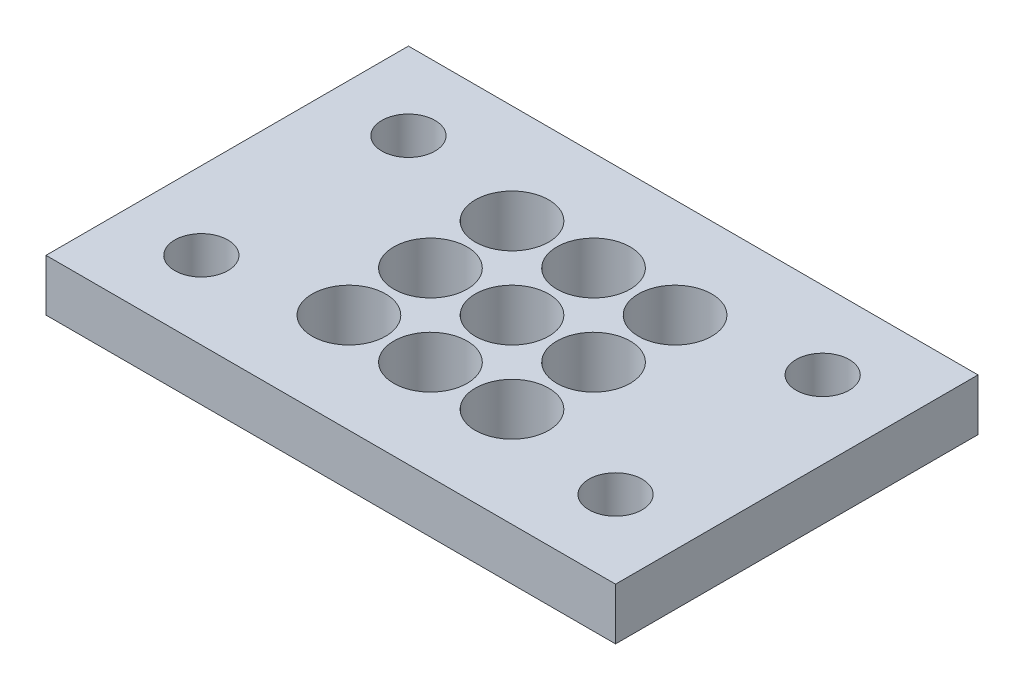
SolidWorks part; units mm, degrees
ref_plane "Front Plane" through (0, 0, 0) normal (0, 0, 1) x (1, 0, 0)
ref_plane "Top Plane" through (0, 0, 0) normal (0, 1, 0) x (1, 0, 0)
ref_plane "Right Plane" through (0, 0, 0) normal (1, 0, 0) x (0, 0, -1)
sketch "Sketch1" plane through (0, 0, 0) normal (0, 1, 0) x (1, 0, 0)
  line L0 (9.525, 34.925) -> (0, 34.925) construction
  line L1 (0, 0) -> (69.85, 0)
  line L2 (0, 0) -> (0, 44.45)
  line L3 (0, 44.45) -> (69.85, 44.45)
  line L4 (69.85, 0) -> (69.85, 44.45)
  line L5 (9.525, 34.925) -> (60.325, 34.925) construction
  line L6 (9.525, 34.925) -> (9.525, 9.525) construction
  line L7 (9.525, 9.525) -> (60.325, 9.525) construction
  line L8 (60.325, 34.925) -> (60.325, 9.525) construction
  line L9 (9.525, 34.925) -> (9.525, 44.45) construction
  circle A0 centre (9.525, 34.925) radius 3.2639
  circle A1 centre (60.325, 34.925) radius 3.2639
  circle A2 centre (9.525, 9.525) radius 3.2639
  circle A3 centre (60.325, 9.525) radius 3.2639
  circle A4 centre (34.925, 22.225) radius 4.5
  circle A5 centre (44.925, 22.225) radius 4.5
  circle A6 centre (44.925, 32.225) radius 4.5
  circle A7 centre (34.925, 32.225) radius 4.5
  circle A8 centre (24.925, 22.225) radius 4.5
  circle A9 centre (24.925, 32.225) radius 4.5
  circle A10 centre (34.925, 32.225) radius 4.5
  circle A11 centre (44.925, 22.225) radius 4.5
  circle A12 centre (44.925, 12.225) radius 4.5
  circle A13 centre (34.925, 12.225) radius 4.5
  circle A14 centre (24.925, 22.225) radius 4.5
  circle A15 centre (24.925, 12.225) radius 4.5
  circle A16 centre (34.925, 12.225) radius 4.5
  point P13 (34.925, 34.925)
  point P14 (34.925, 44.45)
  point P20 (69.85, 22.225)
  dimension "D5" = 6.5278
  dimension "D6" = 9
  dimension "D1" = 69.85
  dimension "D2" = 44.45
  dimension "D3" = 50.8
  dimension "D4" = 25.4
  dimension "D15" = 10
  dimension "D16" = 10
  dimension "D17" = 10
  dimension "D18" = 10
  dimension "D19" = 10
  dimension "D20" = 10
  dimension "D21" = 10
  dimension "D22" = 10
  dimension "D7" = 2
  dimension "D8" = 2
  dimension "D9" = 2
  dimension "D10" = 2
  dimension "D11" = 2
  dimension "D12" = 2
  dimension "D13" = 2
  dimension "D14" = 2
extrude "Boss-Extrude1" add sketch "Sketch1" along normal blind 6.35 contours L1 L4 L3 L2 A15 A13 A12 A9 A8 A7 A6 A5 A4 A3 A2 A1 A0 region at (0.8279, 0, -22.225)
equation "\"o\"= 10mm"
equation "\"P\"= 10"
